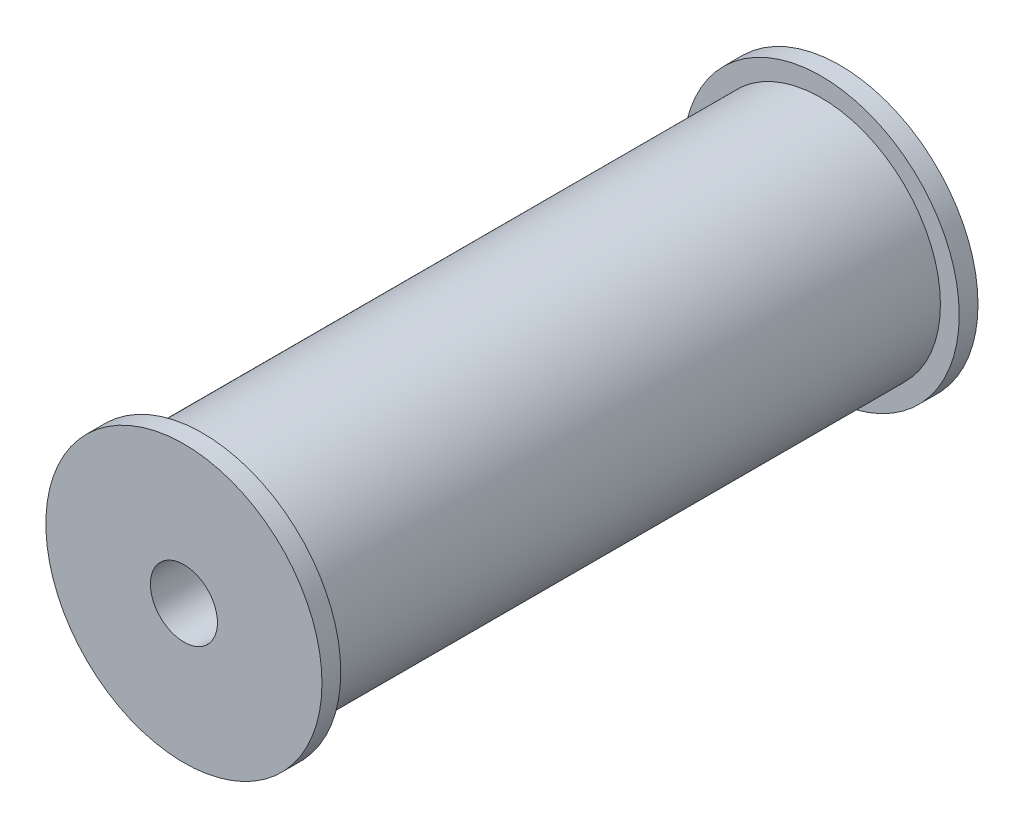
SolidWorks part; units mm, degrees
ref_plane "Front Plane" through (0, 0, 0) normal (0, 0, 1) x (1, 0, 0)
ref_plane "Top Plane" through (0, 0, 0) normal (0, 1, 0) x (1, 0, 0)
ref_plane "Right Plane" through (0, 0, 0) normal (1, 0, 0) x (0, 0, -1)
sketch "Sketch1" plane through (0, 0, 0) normal (0, 0, 1) x (1, 0, 0)
  circle A0 centre (0, 0) radius 12.7
  dimension "D1" = 25.4
extrude "Boss-Extrude1" add sketch "Sketch1" along normal blind 69.85
sketch "Sketch2" plane through (0, 0, 69.85) normal (0, 0, 1) x (1, 0, 0)
  circle A0 centre (0, 0) radius 3.572
  dimension "D1" = 7.144
extrude "Cut-Extrude3" cut sketch "Sketch2" against normal up to surface (69.85 mm away) up to face at (12.7, 0, 0)
sketch "Sketch3" plane through (0, 0, 0) normal (0, 0, 1) x (1, 0, 0)
  circle A0 centre (0, 0) radius 14.7
  circle A1 centre (0, 0) radius 3.572
extrude "Boss-Extrude2" add sketch "Sketch3" along normal blind 2
extrude "Boss-Extrude3" add sketch "Sketch3<2>" against normal blind 2 from surface starting at face at (3.572, 0, 69.85)
sketch "Sketch3<2>" plane through (0, 0, 0) normal (0, 0, 1) x (1, 0, 0) same geometry as "Sketch3"
